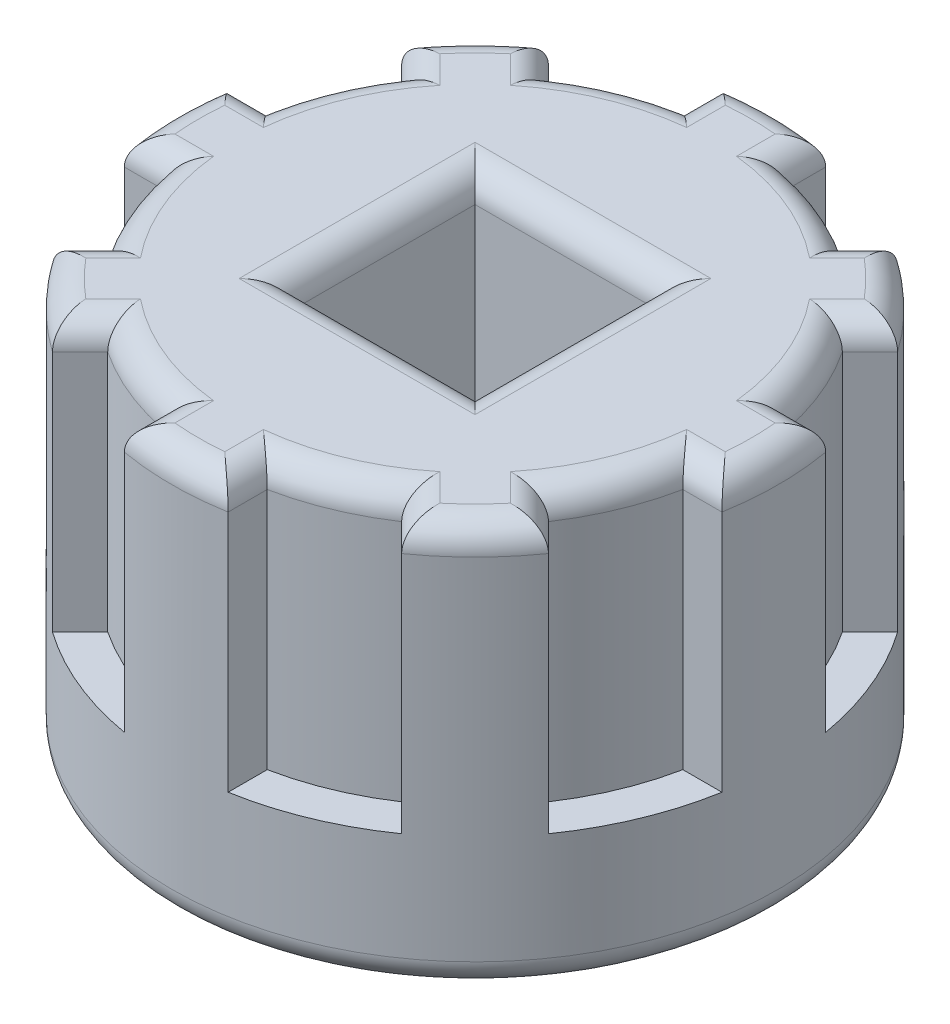
SolidWorks part; units mm, degrees
ref_plane "Front Plane" through (0, 0, 0) normal (0, 0, 1) x (1, 0, 0)
ref_plane "Top Plane" through (0, 0, 0) normal (0, 1, 0) x (1, 0, 0)
ref_plane "Right Plane" through (0, 0, 0) normal (1, 0, 0) x (0, 0, -1)
sketch "Sketch1" plane through (0, 0, 0) normal (0, 1, 0) x (1, 0, 0)
  circle A0 centre (0, 0) radius 5.715
  dimension "D1" = 11.43
extrude "Boss-Extrude2" add sketch "Sketch1" along normal blind 2.54
sketch "Sketch2" plane through (0, 2.54, 0) normal (0, 1, 0) x (1, 0, 0)
  line L0 (-0.9779, 5.6307) -> (-0.9779, 4.8941)
  line L1 (0.9779, 5.6307) -> (0.9779, 4.8941)
  line L2 (3.29, 4.673) -> (2.7692, 4.1521)
  line L3 (4.673, 3.29) -> (4.1521, 2.7692)
  line L4 (5.6307, 0.9779) -> (4.8941, 0.9779)
  line L5 (5.6307, -0.9779) -> (4.8941, -0.9779)
  line L6 (4.673, -3.29) -> (4.1521, -2.7692)
  line L7 (3.29, -4.673) -> (2.7692, -4.1521)
  line L8 (0.9779, -5.6307) -> (0.9779, -4.8941)
  line L9 (-0.9779, -5.6307) -> (-0.9779, -4.8941)
  line L10 (-3.29, -4.673) -> (-2.7692, -4.1521)
  line L11 (-4.673, -3.29) -> (-4.1521, -2.7692)
  line L12 (-5.6307, -0.9779) -> (-4.8941, -0.9779)
  line L13 (-5.6307, 0.9779) -> (-4.8941, 0.9779)
  line L14 (-4.673, 3.29) -> (-4.1521, 2.7692)
  line L15 (-3.29, 4.673) -> (-2.7692, 4.1521)
  circle A0 centre (0, 0) radius 5.715
  circle A1 centre (0, 0) radius 4.9909
  point P37 (0, 0)
  circle M4 centre (0, 0) radius 5.715
  dimension "D2" = 11.43
  dimension "D1" = 0.9779
  dimension "D3" = 0.9779
  dimension "D4" = 0.7366
  dimension "D5" = 0.7366
  dimension "D6" = 8
extrude "Boss-Extrude3" add sketch "Sketch2" along normal blind 5.08 contours A1 | A1 L1 L0 M4 | A1 L15 L14 M4 | A1 L13 L12 M4 | A1 L11 L10 M4 | A1 L9 L8 M4 | A1 L7 L6 M4 | A1 L5 L4 M4 | A1 L3 L2 M4 | A1 region at (0, 2.54, -5.3227) region at (0, 2.54, 0) region at (-3.7637, 2.54, -3.7637) region at (3.7637, 2.54, -3.7637) region at (-5.3227, 2.54, 0) region at (5.3227, 2.54, 0) region at (-3.7637, 2.54, 3.7637) region at (3.7637, 2.54, 3.7637) region at (0, 2.54, 5.3227)
sketch "Sketch3" plane through (0, 7.62, 0) normal (0, 1, 0) x (1, 0, 0)
  line L1 (-1.7145, -1.7145) -> (1.7145, -1.7145)
  line L2 (-1.7145, -1.7145) -> (-1.7145, 1.7145)
  line L3 (-1.7145, 1.7145) -> (1.7145, 1.7145)
  line L4 (1.7145, -1.7145) -> (1.7145, 1.7145)
  line L5 (-1.7145, -1.7145) -> (1.7145, 1.7145) construction
  line L6 (-1.7145, 1.7145) -> (1.7145, -1.7145) construction
  point P0 (0, 0)
  dimension "D1" = 3.429
  dimension "D2" = 3.429
extrude "Cut-Extrude1" cut sketch "Sketch3" against normal through all both and the other way through all
fillet "Fillet1" radius 0.508 41 edges at (0, 0, 5.715) (-1.7145, 0, 0) (0, 0, -1.7145) (1.7145, 0, 0) (0, 0, 1.7145) (0, 7.62, 5.715) (-0.9779, 7.62, 5.2624) (-1.9099, 7.62, 4.6109) (-3.0296, 7.62, 4.4126) (-4.0411, 7.62, 4.0411) (-4.4126, 7.62, 3.0296) (-4.6109, 7.62, 1.9099) (-5.2624, 7.62, 0.9779) (-5.715, 7.62, 0) (-5.2624, 7.62, -0.9779) (-4.6109, 7.62, -1.9099) (-4.4126, 7.62, -3.0296) (-4.0411, 7.62, -4.0411) (-3.0296, 7.62, -4.4126) (-1.9099, 7.62, -4.6109) (-0.9779, 7.62, -5.2624) (0, 7.62, -5.715) (0.9779, 7.62, -5.2624) (1.9099, 7.62, -4.6109) (3.0296, 7.62, -4.4126) (4.0411, 7.62, -4.0411) (4.4126, 7.62, -3.0296) (4.6109, 7.62, -1.9099) (5.2624, 7.62, -0.9779) (5.715, 7.62, 0) (5.2624, 7.62, 0.9779) (4.6109, 7.62, 1.9099) (4.4126, 7.62, 3.0296) (4.0411, 7.62, 4.0411) (3.0296, 7.62, 4.4126) (1.9099, 7.62, 4.6109) (0.9779, 7.62, 5.2624) (0, 7.62, -1.7145) (-1.7145, 7.62, 0) (0, 7.62, 1.7145) (1.7145, 7.62, 0)
